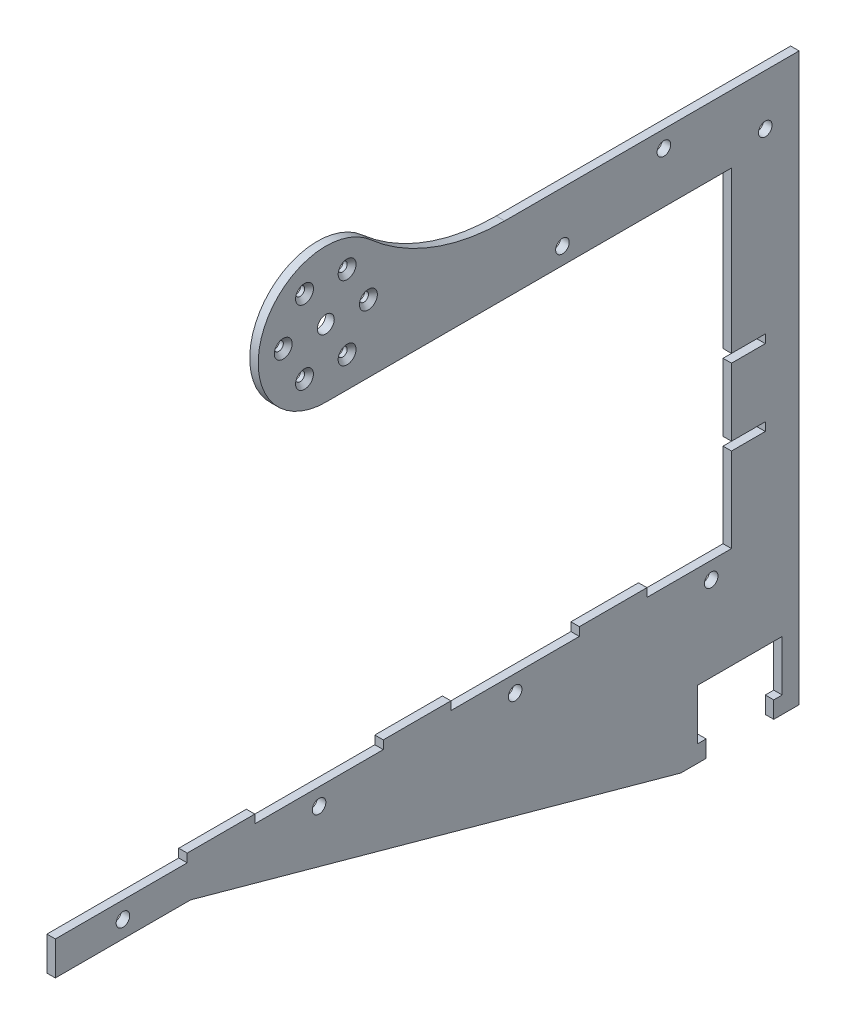
SolidWorks part; units mm, degrees
material "6061-T6 (SS)"
ref_plane "Front Plane" through (0, 0, 0) normal (0, 0, 1) x (1, 0, 0)
ref_plane "Top Plane" through (0, 0, 0) normal (0, 1, 0) x (1, 0, 0)
ref_plane "Right Plane" through (0, 0, 0) normal (1, 0, 0) x (0, 0, -1)
sketch "Sketch1" plane through (0, 0, 0) normal (1, 0, 0) x (0, 0, -1)
  line L0 (0, -80.9625) -> (0, 80.9625)
  line L3 (-177.8, 55.5625) -> (-25.4, 55.5625)
  line L6 (-25.4, 55.5625) -> (-25.4, -68.2625)
  line L7 (-25.4, -68.2625) -> (-279.4, -68.2625)
  line L8 (-279.4, -68.2625) -> (-279.4, -80.9625)
  line L10 (-279.4, -80.9625) -> (-228.6, -80.9625)
  line L12 (-44.45, -131.7625) -> (-34.925, -131.7625)
  line L16 (-9.525, -131.7625) -> (0, -131.7625)
  line L18 (0, -80.9625) -> (0, -131.7625)
  line L20 (-38.1, -106.3625) -> (-38.1, -125.4125)
  line L21 (-38.1, -125.4125) -> (-34.925, -125.4125)
  line L23 (-34.925, -131.7625) -> (-34.925, -125.4125)
  line L24 (-9.525, -131.7625) -> (-9.525, -125.4125)
  line L25 (-9.525, -125.4125) -> (-6.35, -125.4125)
  line L26 (-6.35, -125.4125) -> (-6.35, -106.3625)
  line L28 (-38.1, -106.3625) -> (-6.35, -106.3625)
  line L30 (0, 80.9625) -> (-110.5979, 80.9625)
  line L31 (-279.4, -80.9625) -> (-228.6, -80.9625) construction
  line L33 (-279.4, -74.6125) -> (-177.8, -74.6125) construction
  line L34 (-44.45, -131.7625) -> (-228.6, -80.9625)
  arc A0 (-160.9995, 100.0125) -> (-177.8, 55.5625) centre (-177.8, 80.9625) ccw
  arc A1 (-110.5979, 80.9625) -> (-160.9995, 100.0125) centre (-110.5979, 157.1625) cw
  point P4 (0, 0)
  point P30 (-228.6, -74.6125)
  dimension "D7" = 50.8
  dimension "D3" = 25.4
  dimension "D10" = 25.4
  dimension "D11" = 76.2
  dimension "D1" = 152.4
  dimension "D2" = 12.7
  dimension "D4" = 25.4
  dimension "D5" = 123.825
  dimension "D6" = 254
  dimension "D8" = 31.75
  dimension "D9" = 9.525
  dimension "D12" = 3.175
  dimension "D13" = 19.05
  dimension "D14" = 6.35
  dimension "D16" = 38.1
base flange "Base-Flange1" sketch "Sketch1" thickness 3.175 reverse thickness direction no parameters "D1"=3.175
sketch "Sketch8" plane through (0, 0, 0) normal (1, 0, 0) x (0, 0, -1)
  line L0 (-25.4, -7.9375) -> (-12.7, -7.9375)
  line L1 (-177.8, 55.5625) -> (-25.4, 55.5625) construction
  line L2 (-12.7, -7.9375) -> (-12.7, -4.7625)
  line L3 (-12.7, -4.7625) -> (-25.4, -4.7625)
  line L4 (-25.4, -4.7625) -> (-25.4, -7.9375)
  line L5 (-25.4, -4.7625) -> (-25.4, 55.5625) construction
  line L6 (-25.4, -68.2625) -> (-25.4, -36.5125) construction
  line L7 (-25.4, 55.5625) -> (-25.4, -68.2625) construction
  line L8 (-25.4, -33.3375) -> (-12.7, -33.3375)
  line L9 (-12.7, -33.3375) -> (-12.7, -36.5125)
  line L10 (-12.7, -36.5125) -> (-25.4, -36.5125)
  line L11 (-25.4, -36.5125) -> (-25.4, -33.3375)
  dimension "D1" = 25.4
  dimension "D2" = 63.5
  dimension "D5" = 12.7
  dimension "D6" = 3.175
extrude "Cut-Extrude2" cut sketch "Sketch8" against normal through all normal cut yes
sketch "Sketch11" plane through (0, 0, 0) normal (1, 0, 0) x (0, 0, -1)
  circle A0 centre (-177.8, 80.9625) radius 3.175
  arc A1 (-160.9995, 100.0125) -> (-177.8, 55.5625) centre (-177.8, 80.9625) ccw construction
  dimension "D1" = 6.35
extrude "Cut-Extrude4" cut sketch "Sketch11" against normal through all normal cut yes
sketch "Sketch21" plane through (0, 0, 0) normal (1, 0, 0) x (0, 0, -1)
  line L0 (-25.4, -68.2625) -> (-279.4, -68.2625) construction
  line L2 (-279.4, -68.2625) -> (-279.4, -80.9625) construction
  line L3 (-22.225, -106.3625) -> (-22.225, -64.7412) construction
  line L4 (-38.1, -106.3625) -> (-6.35, -106.3625) construction
  line L5 (0, -131.7625) -> (0, 80.9625) construction
  line L6 (0, 80.9625) -> (-110.5979, 80.9625) construction
  circle A0 centre (-33.02, -74.6125) radius 2.5527
  circle A1 centre (-106.68, -74.6125) radius 2.5527
  circle A2 centre (-180.34, -74.6125) radius 2.5527
  circle A3 centre (-254, -74.6125) radius 2.5527
  circle A8 centre (-12.7, 61.9125) radius 2.5527
  circle A9 centre (-50.8, 74.6125) radius 2.5527
  circle A10 centre (-88.9, 61.9125) radius 2.5527
  dimension "D1" = 6.35
  dimension "D2" = 5.1054
  dimension "D3" = 10.795
  dimension "D5" = 25.4
  dimension "D9" = 50.8
  dimension "D6" = 12.7
  dimension "D7" = 76.2
  dimension "D8" = 12.7
  dimension "D10" = 19.05
  dimension "D4" = 4
extrude "Cut-Extrude5" cut sketch "Sketch21" against normal through all normal cut yes
sketch "Sketch23" plane through (0, 0, 0) normal (1, 0, 0) x (0, 0, -1)
  line L0 (-25.4, -68.2625) -> (-279.4, -68.2625) construction
  line L1 (-229.87, -68.2625) -> (-204.47, -68.2625)
  line L2 (-229.87, -68.2625) -> (-229.87, -65.0875)
  line L3 (-229.87, -65.0875) -> (-204.47, -65.0875)
  line L4 (-204.47, -68.2625) -> (-204.47, -65.0875)
  line L5 (-254, -74.6125) -> (-229.87, -65.0875) construction
  line L6 (-156.21, -68.2625) -> (-130.81, -68.2625)
  line L7 (-156.21, -68.2625) -> (-156.21, -65.0875)
  line L8 (-156.21, -65.0875) -> (-130.81, -65.0875)
  line L9 (-130.81, -68.2625) -> (-130.81, -65.0875)
  line L10 (-82.55, -68.2625) -> (-57.15, -68.2625)
  line L11 (-82.55, -68.2625) -> (-82.55, -65.0875)
  line L12 (-82.55, -65.0875) -> (-57.15, -65.0875)
  line L13 (-57.15, -68.2625) -> (-57.15, -65.0875)
  line L14 (-180.34, -74.6125) -> (-204.47, -65.0875) construction
  line L15 (-180.34, -74.6125) -> (-156.21, -65.0875) construction
  line L16 (-106.68, -74.6125) -> (-82.55, -65.0875) construction
  dimension "D1" = 3.175
  dimension "D2" = 25.4
base flange "Tab1" sketch "Sketch23" thickness 3.175 reverse thickness direction no parameters "D1"=3.175
sketch "Sketch26" plane through (0, 0, 0) normal (1, 0, 0) x (0, 0, -1)
  circle A0 centre (-177.8, 80.9625) radius 16 construction
  point P0 (-161.8, 80.9625)
  point P12 (-169.8, 67.1061)
  point P13 (-185.8, 67.1061)
  point P14 (-193.8, 80.9625)
  point P15 (-185.8, 94.8189)
  point P16 (-169.8, 94.8189)
  dimension "D1" = 32
  dimension "D2" = 6
hole_wizard "CSK for M3 SFHCS1" positions "Sketch26" profile "Sketch25" countersink size "M3" standard "ANSI Metric" end condition up to next
sketch "Sketch25" plane through (0, 80.9625, 161.8) normal (0, 1, 0) x (0, 0, -1)
  line L0 (0, 0) -> (0, 3.175)
  line L1 (0, 3.175) -> (1.7, 3.175)
  line L2 (1.7, 3.175) -> (1.7, 1.66)
  line L3 (1.7, 1.66) -> (3.36, 0)
  line L5 (3.36, 0) -> (0, 0)
  line L6 (-1.7, 1.66) -> (-3.36, 0) construction
  line L11 (0, -6.35) -> (0, 107.95) construction
  dimension "Thru Hole Dia." = 3.4
  dimension "Thru Hole Depth" = 3.175
  dimension "Near C'Sink Dia." = 6.72
  dimension "Near C'Sink Angle" = 90
sketch "Sketch27" plane through (0, 0, 0) normal (1, 0, 0) x (0, 0, -1)
  line L0 (-22.225, -106.3625) -> (-22.225, -84.1375) construction
  line L1 (-38.1, -106.3625) -> (-6.35, -106.3625) construction
  line L10 (-33.02, -74.6125) -> (-11.43, -74.6125) construction
  line L11 (-8.89, -88.1063) -> (-35.56, -88.1063) construction
  line L12 (-8.89, -88.1063) -> (-8.89, -80.1688) construction
  line L13 (-8.89, -80.1688) -> (-35.56, -80.1688) construction
  line L14 (-35.56, -88.1063) -> (-35.56, -80.1688) construction
  line L15 (-8.89, -88.1063) -> (-35.56, -80.1688) construction
  line L16 (-8.89, -80.1688) -> (-35.56, -88.1063) construction
  line L17 (-22.225, -84.1375) -> (-46.5451, -84.1375) construction
  line L18 (-33.782, -79.4068) -> (-28.4466, -79.4068)
  line L19 (-35.56, -81.1848) -> (-35.56, -87.0903)
  line L20 (-8.89, -81.1848) -> (-8.89, -87.0903)
  line L21 (-10.668, -79.4068) -> (-16.0034, -79.4068)
  line L22 (-26.9875, -80.1688) -> (-17.4625, -80.1688)
  line L23 (-10.668, -88.8683) -> (-16.0034, -88.8683)
  line L24 (-26.9875, -88.1063) -> (-17.4625, -88.1063)
  line L25 (-33.782, -88.8683) -> (-28.4466, -88.8683)
  circle A0 centre (-11.43, -74.6125) radius 2.5527
  circle A1 centre (-11.43, -93.6625) radius 2.5527
  circle A2 centre (-33.02, -93.6625) radius 2.5527
  arc A3 (-28.4466, -79.4068) -> (-26.9875, -80.1688) centre (-28.4466, -81.1848) cw
  arc A4 (-33.782, -79.4068) -> (-35.56, -81.1848) centre (-33.782, -81.1848) ccw
  arc A5 (-16.0034, -79.4068) -> (-17.4625, -80.1688) centre (-16.0034, -81.1848) ccw
  arc A6 (-10.668, -79.4068) -> (-8.89, -81.1848) centre (-10.668, -81.1848) cw
  arc A7 (-10.668, -88.8683) -> (-8.89, -87.0903) centre (-10.668, -87.0903) ccw
  arc A8 (-16.0034, -88.8683) -> (-17.4625, -88.1063) centre (-16.0034, -87.0903) cw
  arc A9 (-28.4466, -88.8683) -> (-26.9875, -88.1063) centre (-28.4466, -87.0903) ccw
  arc A10 (-33.782, -88.8683) -> (-35.56, -87.0903) centre (-33.782, -87.0903) cw
  dimension "D1" = 22.225
  dimension "D5" = 5.1054
  dimension "D6" = 1.778
  dimension "D2" = 7.9375
  dimension "D3" = 26.67
  dimension "D4" = 21.59
  dimension "D7" = 9.525
  dimension "D8" = 0.762
extrude "Cut-Extrude6" [suppressed] cut sketch "Sketch27" against normal through all
sketch "Bend-Lines1" [suppressed] plane through (0, 0, 0) normal (0, 1, 0) x (1, 0, 0)
sketch "Bounding-Box1" [suppressed] plane through (0, 0, 0) normal (0, 1, 0) x (1, 0, 0)
sheet metal parameters "Sheet-Metal1" thickness 3.175 parameters "D1"=3.175
flat pattern "Flat-Pattern1" [suppressed]
sketch "Bend-Lines2" plane through (0, 0, 0) normal (0, 1, 0) x (1, 0, 0)
sketch3d "Bounding-Box2" [suppressed]
  line L0 (-25.4, 25.4, 0) -> (330.2, 25.4, 0) construction
  line L1 (-25.4, -180.975, 0) -> (330.2, -180.975, 0) construction
  line L2 (-25.4, 25.4, 0) -> (-25.4, -180.975, 0) construction
  line L3 (330.2, 25.4, 0) -> (330.2, -180.975, 0) construction
sheet metal parameters "Sheet-Metal4" thickness 3.175 parameters "D1"=3.175
flat pattern "Flat-Pattern1"
sketch "Bend-Lines2" plane through (0, 0, 0) normal (0, 1, 0) x (1, 0, 0)
sketch3d "Bounding-Box2" [suppressed]
  line L0 (-25.4, 25.4, 0) -> (203.2, 25.4, 0) construction
  line L1 (-25.4, -180.975, 0) -> (203.2, -180.975, 0) construction
  line L2 (-25.4, 25.4, 0) -> (-25.4, -180.975, 0) construction
  line L3 (203.2, 25.4, 0) -> (203.2, -180.975, 0) construction
sheet metal parameters "Sheet-Metal6" thickness 3.175 parameters "D1"=3.175
flat pattern "Flat-Pattern1" [suppressed]
sketch "Bend-Lines2" plane through (0, 0, 0) normal (0, 1, 0) x (1, 0, 0)
sketch3d "Bounding-Box2" [suppressed]
  line L0 (-25.4, 25.4, 0) -> (203.2, 25.4, 0) construction
  line L1 (-25.4, -180.975, 0) -> (203.2, -180.975, 0) construction
  line L2 (-25.4, 25.4, 0) -> (-25.4, -180.975, 0) construction
  line L3 (203.2, 25.4, 0) -> (203.2, -180.975, 0) construction
sketch "Sketch14-1" [suppressed] plane through (-3.175, 0, 0) normal (-1, 0, 0) x (0, 0, 1)
  circle A0 centre (203.2, 77.7875) radius 16 construction
  circle A1 centre (203.2, 77.7875) radius 16 construction
  circle A2 centre (203.2, 77.7875) radius 16 construction
  circle A3 centre (203.2, 77.7875) radius 16 construction
  circle A4 centre (203.2, 77.7875) radius 16 construction
  circle A5 centre (203.2, 77.7875) radius 16 construction
  point P5 (203.2, 93.7875)
  dimension "D1" = 32
  dimension "D2" = 6
sheet metal parameters "Sheet-Metal12" thickness 3.175 parameters "D1"=3.175
flat pattern "Flat-Pattern12"
sketch "Bend-Lines3" plane through (0, 0, 0) normal (0, 1, 0) x (1, 0, 0)
sketch3d "Bounding-Box3" [suppressed]
  line L0 (177.8, -73.025, 0) -> (177.8, -104.775, 0) construction
  line L1 (152.4, -73.025, 0) -> (152.4, -104.775, 0) construction
  line L2 (177.8, -73.025, 0) -> (152.4, -73.025, 0) construction
  line L3 (177.8, -104.775, 0) -> (152.4, -104.775, 0) construction
sheet metal parameters "Sheet-Metal13" thickness 3.175 parameters "D1"=3.175
flat pattern "Flat-Pattern13"
sketch "Bend-Lines4" plane through (0, 0, 0) normal (0, 1, 0) x (1, 0, 0)
sketch3d "Bounding-Box4" [suppressed]
  line L0 (-50.8, -231.775, 0) -> (177.8, -231.775, 0) construction
  line L1 (-50.8, -107.95, 0) -> (177.8, -107.95, 0) construction
  line L2 (-50.8, -231.775, 0) -> (-50.8, -107.95, 0) construction
  line L3 (177.8, -231.775, 0) -> (177.8, -107.95, 0) construction
sheet metal parameters "Sheet-Metal14" thickness 3.175 parameters "D1"=3.175
flat pattern "Flat-Pattern14"
sketch "Bend-Lines5" plane through (0, 0, 0) normal (0, 1, 0) x (1, 0, 0)
sketch "Bounding-Box5" [suppressed] plane through (0, 0, 0) normal (0, 1, 0) x (1, 0, 0)
sheet metal parameters "Sheet-Metal15" thickness 3.175 parameters "D1"=3.175
flat pattern "Flat-Pattern1" [suppressed]
sketch "Bend-Lines2" plane through (0, 0, 0) normal (0, 1, 0) x (1, 0, 0)
sketch3d "Bounding-Box2" [suppressed]
  line L0 (109.6908, -298.3849, 0) -> (-172.9856, -257.5841, 0) construction
  line L1 (141.1244, -80.6061, 0) -> (-141.5519, -39.8053, 0) construction
  line L2 (109.6908, -298.3849, 0) -> (141.1244, -80.6061, 0) construction
  line L3 (-172.9856, -257.5841, 0) -> (-141.5519, -39.8053, 0) construction
sketch "Sketch14-1" plane through (-3.175, 0, 0) normal (-1, 0, 0) x (0, 0, 1)
  circle A0 centre (177.8, 82.55) radius 16 construction
  circle A1 centre (177.8, 82.55) radius 16 construction
  circle A2 centre (177.8, 82.55) radius 16 construction
  circle A3 centre (177.8, 82.55) radius 16 construction
  circle A4 centre (177.8, 82.55) radius 16 construction
  circle A5 centre (177.8, 82.55) radius 16 construction
  point P44 (193.8, 82.55)
  point P51 (185.8, 68.6936)
  point P52 (169.8, 68.6936)
  point P53 (161.8, 82.55)
  point P54 (169.8, 96.4064)
  point P55 (185.8, 96.4064)
  dimension "D1" = 32
  dimension "D2" = 6
  dimension "D3" = 6
sheet metal parameters "Sheet-Metal16" thickness 3.175 parameters "D1"=3.175
flat pattern "Flat-Pattern16"
sketch "Bend-Lines6" plane through (0, 0, 0) normal (0, 1, 0) x (1, 0, 0)
sketch3d "Bounding-Box6" [suppressed]
  line L0 (109.6908, -298.3849, 0) -> (-172.9856, -257.5841, 0) construction
  line L1 (141.1244, -80.6061, 0) -> (-141.5519, -39.8053, 0) construction
  line L2 (109.6908, -298.3849, 0) -> (141.1244, -80.6061, 0) construction
  line L3 (-172.9856, -257.5841, 0) -> (-141.5519, -39.8053, 0) construction
sheet metal parameters "Sheet-Metal17" thickness 3.175 parameters "D1"=3.175
flat pattern "Flat-Pattern16"
sketch "Bend-Lines6" plane through (0, 0, 0) normal (0, 1, 0) x (1, 0, 0)
sketch3d "Bounding-Box6" [suppressed]
  line L0 (109.6908, -295.2099, 0) -> (-172.9856, -254.4091, 0) construction
  line L1 (140.6755, -80.5413, 0) -> (-142.0008, -39.7405, 0) construction
  line L2 (109.6908, -295.2099, 0) -> (140.6755, -80.5413, 0) construction
  line L3 (-172.9856, -254.4091, 0) -> (-142.0008, -39.7405, 0) construction
sheet metal parameters "Sheet-Metal18" thickness 3.175 parameters "D1"=3.175
flat pattern "Flat-Pattern16"
sketch "Bend-Lines6" plane through (0, 0, 0) normal (0, 1, 0) x (1, 0, 0)
sketch3d "Bounding-Box6" [suppressed]
  line L0 (109.6908, -295.2099, 0) -> (-172.9856, -254.4091, 0) construction
  line L1 (140.6755, -80.5413, 0) -> (-142.0008, -39.7405, 0) construction
  line L2 (109.6908, -295.2099, 0) -> (140.6755, -80.5413, 0) construction
  line L3 (-172.9856, -254.4091, 0) -> (-142.0008, -39.7405, 0) construction
